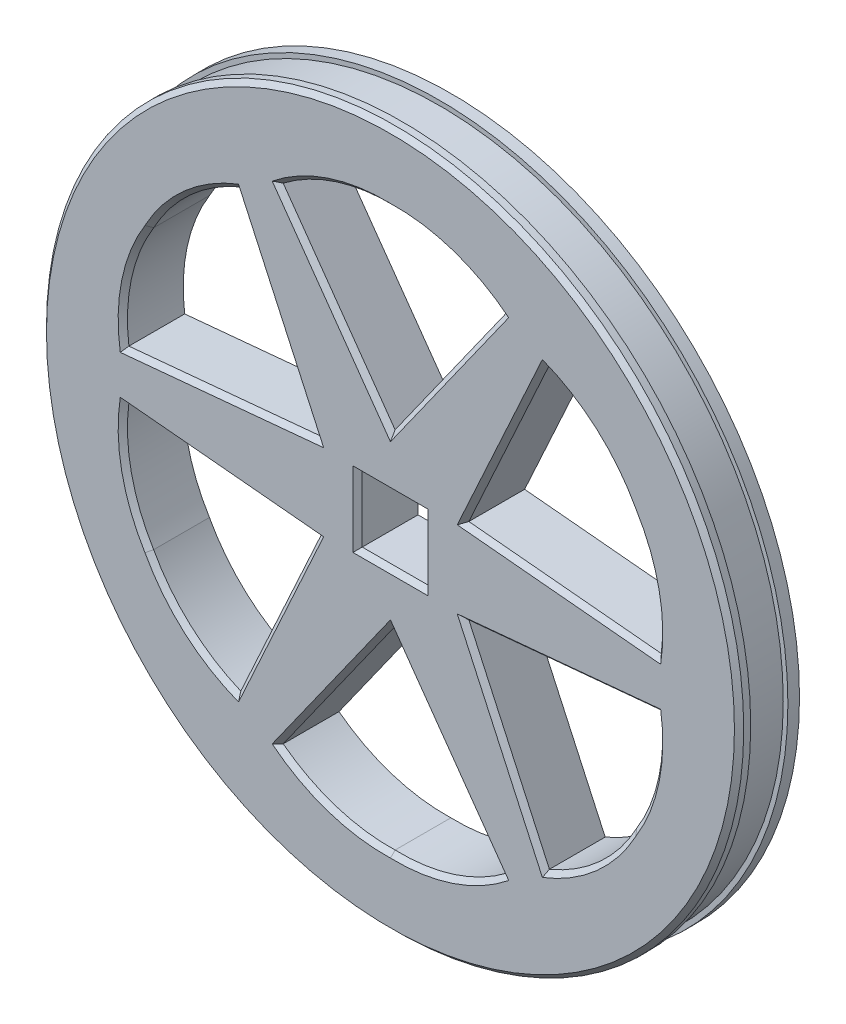
SolidWorks part; units mm, degrees
ref_plane "Front Plane" through (0, 0, 0) normal (0, 0, 1) x (1, 0, 0)
ref_plane "Top Plane" through (0, 0, 0) normal (0, 1, 0) x (1, 0, 0)
ref_plane "Right Plane" through (0, 0, 0) normal (1, 0, 0) x (0, 0, -1)
sketch "Sketch1" plane through (0, 0, 0) normal (0, 0, 1) x (1, 0, 0)
  line L1 (3.5355, -3.5355) -> (-3.5355, -3.5355)
  line L2 (3.5355, -3.5355) -> (3.5355, 3.5355)
  line L3 (3.5355, 3.5355) -> (-3.5355, 3.5355)
  line L4 (-3.5355, -3.5355) -> (-3.5355, 3.5355)
  line L5 (3.5355, -3.5355) -> (-3.5355, 3.5355) construction
  line L6 (3.5355, 3.5355) -> (-3.5355, -3.5355) construction
  circle A0 centre (0, 0) radius 37.5
  circle A1 centre (0, 0) radius 5 construction
  dimension "D1" = 75
  dimension "D2" = 10
extrude "Boss-Extrude1" add sketch "Sketch1" along normal mid plane 6.5
sketch "Sketch2" plane through (0, 0, 0) normal (0, 0, 1) x (1, 0, 0)
  line L0 (0, 0) -> (0, 32.5712) construction
  line L1 (0, 9.1586) -> (-12.0371, 26.1152)
  line L2 (0, 9.1586) -> (12.0371, 26.1152)
  arc A0 (-12.0371, 26.1152) -> (0, 29.9881) centre (-0.5568, 11.0765) cw
  arc A1 (12.0371, 26.1152) -> (0, 29.9881) centre (0.5568, 11.0765) ccw
extrude "Cut-Extrude1" cut sketch "Sketch2" along normal mid plane 8
pattern_circular "CirPattern1" count 6 over 360 about axis through (0, 0, 3.25) along (0, 0, -1) of "Cut-Extrude1" reverse direction yes
sketch "Sketch3" plane through (0, 0, 0) normal (0, 0, 1) x (1, 0, 0)
  circle A0 centre (0, 0) radius 37.5
  circle A1 centre (0, 0) radius 37
  circle A2 centre (0, 0) radius 37.5 construction
  dimension "D1" = 0.5
extrude "Cut-Extrude2" cut sketch "Sketch3" against normal mid plane 4
chamfer "Chamfer1" distance 0.5 angle 45 29 edges at (6.3517, -29.087, 3.25) (6.0185, -17.6369, 3.25) (-6.0185, -17.6369, 3.25) (-6.3517, -29.087, 3.25) (-22.0143, -20.0442, 3.25) (-12.2648, -14.0307, 3.25) (-18.2833, -3.6063, 3.25) (-28.3659, -9.0428, 3.25) (28.3659, -9.0428, 3.25) (18.2833, -3.6063, 3.25) (12.2648, -14.0307, 3.25) (22.0143, -20.0442, 3.25) (22.0143, 20.0442, 3.25) (12.2648, 14.0307, 3.25) (18.2833, 3.6063, 3.25) (28.3659, 9.0428, 3.25) (-28.3659, 9.0428, 3.25) (-18.2833, 3.6063, 3.25) (-12.2648, 14.0307, 3.25) (-22.0143, 20.0442, 3.25) (-6.3517, 29.087, 3.25) (-6.0185, 17.6369, 3.25) (6.0185, 17.6369, 3.25) (6.3517, 29.087, 3.25) (3.5355, 0, 3.25) (0, 3.5355, 3.25) (-3.5355, 0, 3.25) (0, -3.5355, 3.25) (37.5, 0, 3.25)
